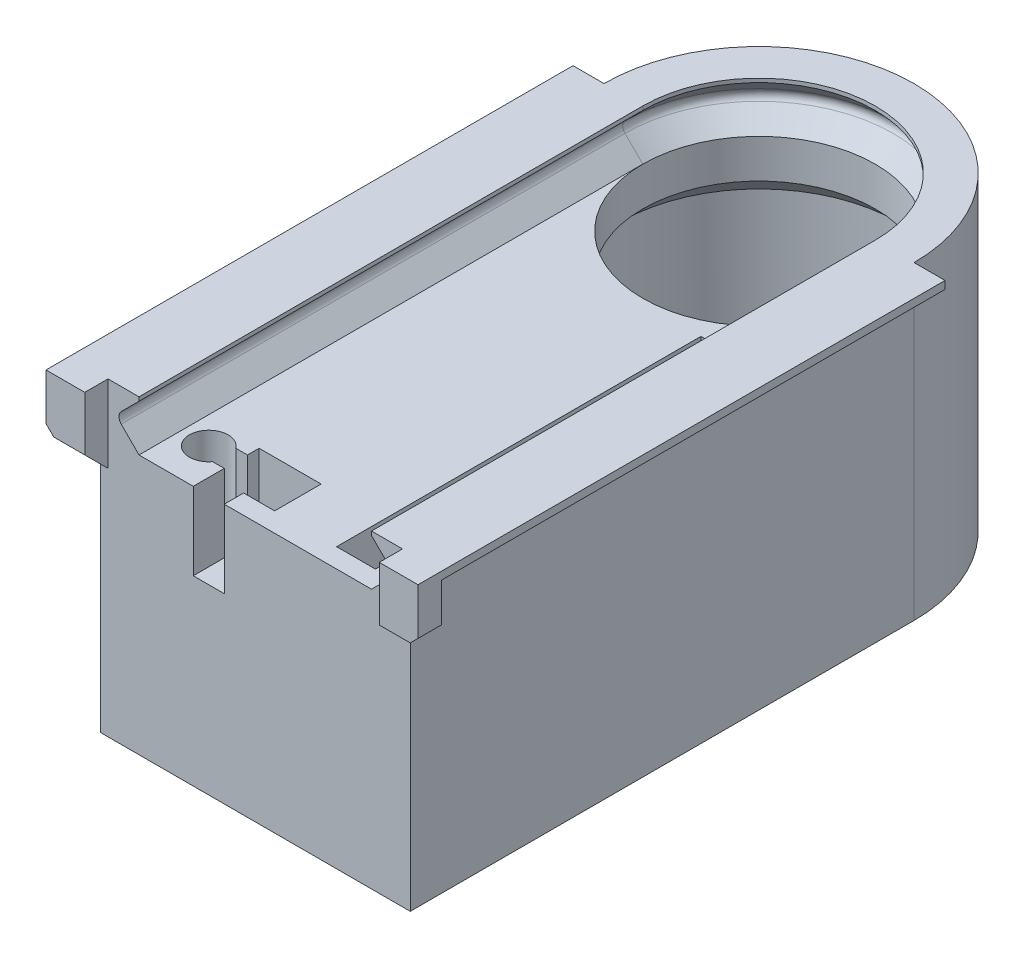
SolidWorks part; units mm, degrees
ref_plane "Płaszczyzna przednia" through (0, 0, 0) normal (0, 0, 1) x (1, 0, 0)
ref_plane "Płaszczyzna górna" through (0, 0, 0) normal (0, 1, 0) x (1, 0, 0)
ref_plane "Płaszczyzna prawa" through (0, 0, 0) normal (1, 0, 0) x (0, 0, -1)
sketch "Szkic1" plane through (0, 0, 0) normal (0, 1, 0) x (1, 0, 0)
  line L0 (0, -32.5) -> (0, 52.5) construction
  line L1 (-20, 32.5) -> (20, 32.5)
  line L2 (-20, 32.5) -> (-20, -32.5)
  line L3 (-20, -32.5) -> (20, -32.5)
  line L4 (20, 32.5) -> (20, -32.5)
  line L5 (-20, 32.5) -> (20, -32.5) construction
  line L6 (-20, -32.5) -> (20, 32.5) construction
  circle A0 centre (0, 32.5) radius 20
  point P0 (0, 0)
  dimension "D1" = 40
  dimension "D2" = 85
extrude "Dodanie-wyciągnięcie1" add sketch "Szkic1" along normal blind 40 contours A0 L2 L3 L4 | L1 A0 | A0 region at (0, 0, -40.9883) region at (0, 0, 7.6519)
sketch "Szkic2" plane through (0, 40, 0) normal (0, 1, 0) x (1, 0, 0)
  line L3 (-15, -32.5) -> (15, -32.5)
  line L5 (15, -32.5) -> (15, 32.5)
  line L6 (-15, 32.5) -> (-15, -32.5)
  line L7 (15, -32.5) -> (15, 32.5)
  line L8 (-15, 32.5) -> (-15, -32.5)
  arc A5 (15, 32.5) -> (-15, 32.5) centre (0, 32.5) ccw
  arc A6 (15, 32.5) -> (-15, 32.5) centre (0, 32.5) ccw
  dimension "D1" = 5
extrude "Wytnij-wyciągnięcie1" cut sketch "Szkic2" against normal blind 6.5
sketch "Szkic4" plane through (0, 0, 32.5) normal (0, 0, 1) x (1, 0, 0)
  line L0 (15, 33.5) -> (18, 36.5)
  line L1 (18, 36.5) -> (15, 39.5)
  line L2 (15, 33.5) -> (15, 40) construction
  line L3 (15, 39.5) -> (15, 33.5)
  dimension "D1" = 6
  dimension "D2" = 45
sketch "Szkic5" plane through (0, 40, 0) normal (0, 1, 0) x (1, 0, 0)
  line L0 (15, -32.5) -> (15, 32.5) construction
  line L1 (-15, 32.5) -> (-15, -32.5) construction
  line L2 (15, -32.5) -> (15, 32.5)
  line L3 (-15, 32.5) -> (-15, -32.5)
  arc A0 (15, 32.5) -> (-15, 32.5) centre (0, 32.5) ccw construction
  arc A1 (15, 32.5) -> (-15, 32.5) centre (0, 32.5) ccw
sweep "Wycięcie-wyciągnięcie po ścieżce1" cut profiles "Szkic4" path "Szkic5"
sketch "Szkic6" plane through (0, 33.5, 0) normal (0, 1, 0) x (1, 0, 0)
  circle A0 centre (0, 32.5) radius 15
extrude "Wytnij-wyciągnięcie2" cut sketch "Szkic6" against normal blind 30
sketch "Szkic7" plane through (0, 3.5, 0) normal (0, 1, 0) x (1, 0, 0)
  circle A0 centre (0, 32.5) radius 18
  arc A5 (20, 32.5) -> (-20, 32.5) centre (0, 32.5) ccw construction
  dimension "D1" = 2
extrude "Wytnij-wyciągnięcie4" cut sketch "Szkic7" along normal blind 20
chamfer "Sfazowanie1" distance 5 angle 45 1 edges at (0, 23.5, -17.5)
sketch "Szkic8" plane through (0, 33.5, 0) normal (0, 1, 0) x (1, 0, 0)
  line L0 (-15, -32.5) -> (15, -32.5) construction
  line L1 (13, 17) -> (8, 17)
  line L2 (13, 17) -> (13, -30)
  line L3 (13, -30) -> (8, -30)
  line L4 (8, 17) -> (8, -30)
  line L5 (13, 17) -> (8, -30) construction
  line L6 (13, -30) -> (8, 17) construction
  line L7 (15, -32.5) -> (15, 32.5) construction
  point P0 (10.5, -6.5)
  point P7 (13.6999, -30)
  point P8 (13.0829, -30)
  dimension "D1" = 5
  dimension "D2" = 2.5
  dimension "D3" = 47
  dimension "D4" = 2
extrude "Wytnij-wyciągnięcie5" cut sketch "Szkic8" against normal blind 5
fillet "Zaokrąglenie2" radius 1 3 edges at (-18, 36.5, 0) (0, 36.5, -50.5) (18, 36.5, 0)
ref_plane "Płaszczyzna1" through (15, 40, 32.5) normal (0, 0, -1) x (-1, 0, 0)
sketch "Szkic10" plane through (0, 33.5, 0) normal (0, 1, 0) x (1, 0, 0)
  line L0 (-4, -27) -> (-11.5, -27) construction
  line L1 (0, -30) -> (-8, -30)
  line L2 (0, -30) -> (0, -24)
  line L3 (0, -24) -> (-8, -24)
  line L4 (-8, -30) -> (-8, -24)
  line L5 (0, -30) -> (-8, -24) construction
  line L6 (0, -24) -> (-8, -30) construction
  line L7 (8, -30) -> (13, -30) construction
  line L8 (-9.5, -25.5) -> (-8, -25.5)
  line L9 (-9.5, -25.5) -> (-9.5, -28.5)
  line L10 (-9.5, -28.5) -> (-8, -28.5)
  line L11 (-8, -25.5) -> (-8, -28.5)
  line L12 (-9.5, -25.5) -> (-8, -28.5) construction
  line L13 (-9.5, -28.5) -> (-8, -25.5) construction
  line L14 (0, 0) -> (0, -32.5) construction
  line L15 (32.875, -32.5) -> (-2.875, -32.5) construction
  circle A0 centre (-11.5, -27) radius 2.5
  point P0 (-4, -27)
  point P8 (-8.75, -27)
  point P13 (0, -30)
  dimension "D3" = 5
  dimension "D1" = 8
  dimension "D2" = 6
  dimension "D4" = 1.5
  dimension "D5" = 3
extrude "Wytnij-wyciągnięcie6" cut sketch "Szkic10" against normal blind 10 contours L9 A0 | L4 L1 L2 L3 | A0 L10 L4 L8 | L9 A0 region at (-4, 33.5, 27) region at (-8.5889, 33.5, 27) region at (-11.6209, 33.5, 27) region at (-9.2982, 33.5, 27)
sketch "Szkic11" plane through (0, 23.5, 0) normal (0, 1, 0) x (1, 0, 0)
  circle A0 centre (-11.5, -27) radius 2.5
extrude "Wytnij-wyciągnięcie7" cut sketch "Szkic11" against normal blind 21
sketch "Szkic12" plane through (0, 33.5, 0) normal (0, 1, 0) x (1, 0, 0)
  line L0 (-15, -32.5) -> (15, -32.5) construction
  line L1 (-8, -30) -> (-4, -30)
  line L2 (-8, -30) -> (-8, -32.5)
  line L3 (-8, -32.5) -> (-4, -32.5)
  line L4 (-4, -30) -> (-4, -32.5)
  dimension "D1" = 4
extrude "Wytnij-wyciągnięcie8" cut sketch "Szkic12" against normal up to surface (10 mm away) up to face at (-6.3125, 23.5, 27)
sketch "Szkic13" plane through (0, 0, 32.5) normal (0, 0, 1) x (1, 0, 0)
  line L0 (-20, 40) -> (-24, 40)
  line L1 (-20, 40) -> (-20, 0) construction
  line L2 (-24, 40) -> (-24, 39)
  line L3 (-24, 39) -> (-20, 35)
  line L4 (-20, 35) -> (-20, 40)
  line L5 (0, 0) -> (0, 45.7075) construction
  line L6 (-20, 0) -> (20, 0) construction
  line L7 (20, 35) -> (20, 40)
  line L8 (24, 39) -> (20, 35)
  line L9 (24, 40) -> (24, 39)
  line L10 (20, 40) -> (24, 40)
  dimension "D1" = 4
  dimension "D2" = 1
  dimension "D3" = 45
extrude "Dodanie-wyciągnięcie2" add sketch "Szkic13" against normal up to vertex (65 mm away) up to point (-20, 40, -32.5)
sketch "Szkic16" plane through (0, 0, 32.5) normal (0, 0, 1) x (1, 0, 0)
  line L0 (-24, 40) -> (-24, 39) construction
  line L1 (-24, 40) -> (-19, 40)
  line L2 (-24, 40) -> (-24, 30)
  line L3 (-24, 30) -> (-19, 30)
  line L4 (-19, 40) -> (-19, 30)
  point P6 (-19.1067, 31.6626)
  dimension "D1" = 5
  dimension "D2" = 10
extrude "Dodanie-wyciągnięcie3" add sketch "Szkic16" along normal blind 3
chamfer "Sfazowanie4" distance 4 angle 45 1 edges at (-24, 30, 34)
chamfer "Sfazowanie5" distance 3 angle 45 1 edges at (-19.5, 30, 35.5)
mirror "Lustro9" about plane through (0, 0, 0) normal (1, 0, 0) of "Sfazowanie5", "Sfazowanie4", "Dodanie-wyciągnięcie3"
